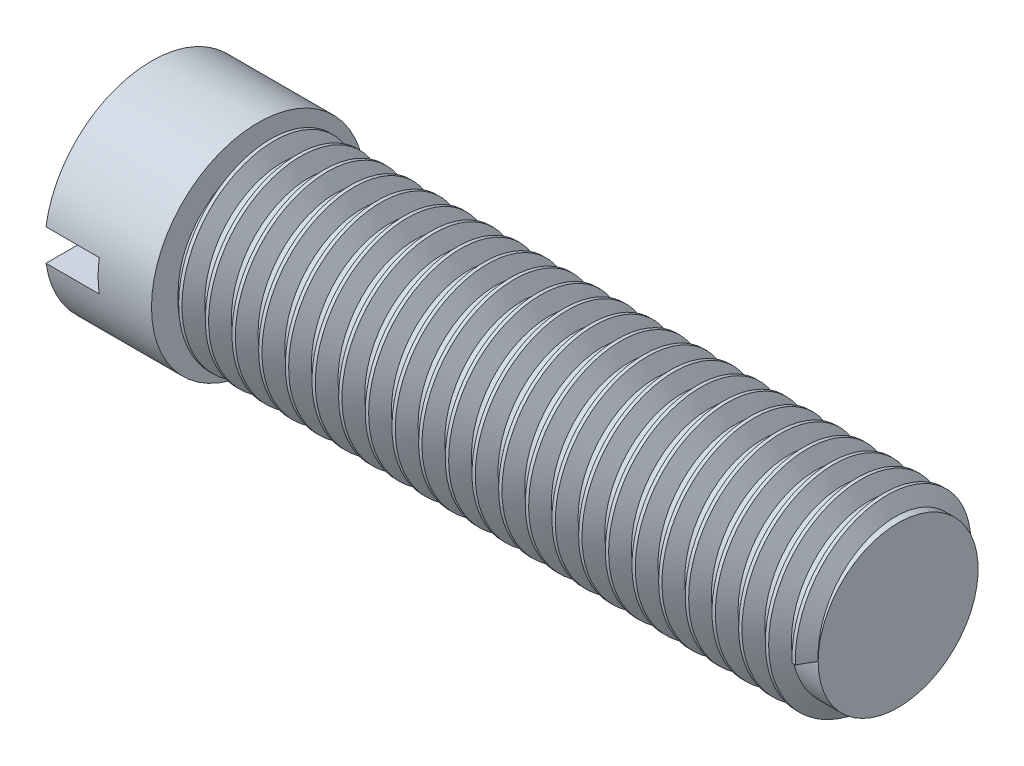
SolidWorks part; units mm, degrees
ref_plane "Front Plane" through (0, 0, 0) normal (0, 0, 1) x (1, 0, 0)
ref_plane "Top Plane" through (0, 0, 0) normal (0, 1, 0) x (1, 0, 0)
ref_plane "Right Plane" through (0, 0, 0) normal (1, 0, 0) x (0, 0, -1)
sketch "Sketch1" plane through (0, 0, 0) normal (0, 0, 1) x (1, 0, 0)
  line L0 (-7, 0) -> (7, 0)
  line L1 (-7, 0) -> (-7, 2)
  line L2 (-7, 2) -> (-5, 2)
  line L3 (-5, 2) -> (-5, 1.5)
  line L4 (-5, 1.5) -> (7, 1.5)
  line L5 (7, 1.5) -> (7, 0)
  point P3 (0, 0)
  dimension "D1" = 14
  dimension "D2" = 2
  dimension "D3" = 1.5
revolve "Revolve1" add sketch "Sketch1" angle 360 about L0
sketch "Sketch2" plane through (0, 0, 0) normal (0, 0, 1) x (1, 0, 0)
  line L0 (-7, 2) -> (-7, -2) construction
  line L2 (-8, 0.2959) -> (-6, 0.2959)
  line L3 (-8, 0.2959) -> (-8, -0.2959)
  line L4 (-8, -0.2959) -> (-6, -0.2959)
  line L5 (-6, 0.2959) -> (-6, -0.2959)
  line L6 (-8, 0.2959) -> (-6, -0.2959) construction
  line L7 (-8, -0.2959) -> (-6, 0.2959) construction
  point P1 (-7, 0)
  point P7 (-4.5014, -0.2959)
  point P9 (-4.5014, 0.2959)
  point P10 (-4.5014, -0.2959)
  dimension "D1" = 2
  dimension "D2" = 0.2959
extrude "Cut-Extrude1" cut sketch "Sketch2" against normal through all both and the other way through all
thread "Thread1" pitch 0.5 method extrude profile "Thread Profile1" start angle 0, offset 0, length 12, pitch 0.5, diameter 3
ref_plane "Plane1" through (7, 0, 1.5) normal (0, -1, 0) x (0, 0, 1)
sketch "Thread Profile1" plane through (7, 0, 1.5) normal (0, -1, 0) x (0, 0, 1)
  line L0 (0, 0) -> (0, 0.5) construction
  line L1 (0, 0) -> (0.2706, 0.1562)
  line L2 (0.2706, 0.1562) -> (0.2706, 0.2187)
  line L3 (0.2706, 0.2187) -> (0, 0.375)
  line L4 (0.2706, 0.1875) -> (0, 0.1875) construction
  line L11 (0, 0) -> (0, 0.375)
  point P2 (0, 0)
  dimension "Pitch" = 0.5
  dimension "Profile_Angle" = 60
  dimension "Profile_Land" = 0.0625
  dimension "Profile_Height" = 0.2706
